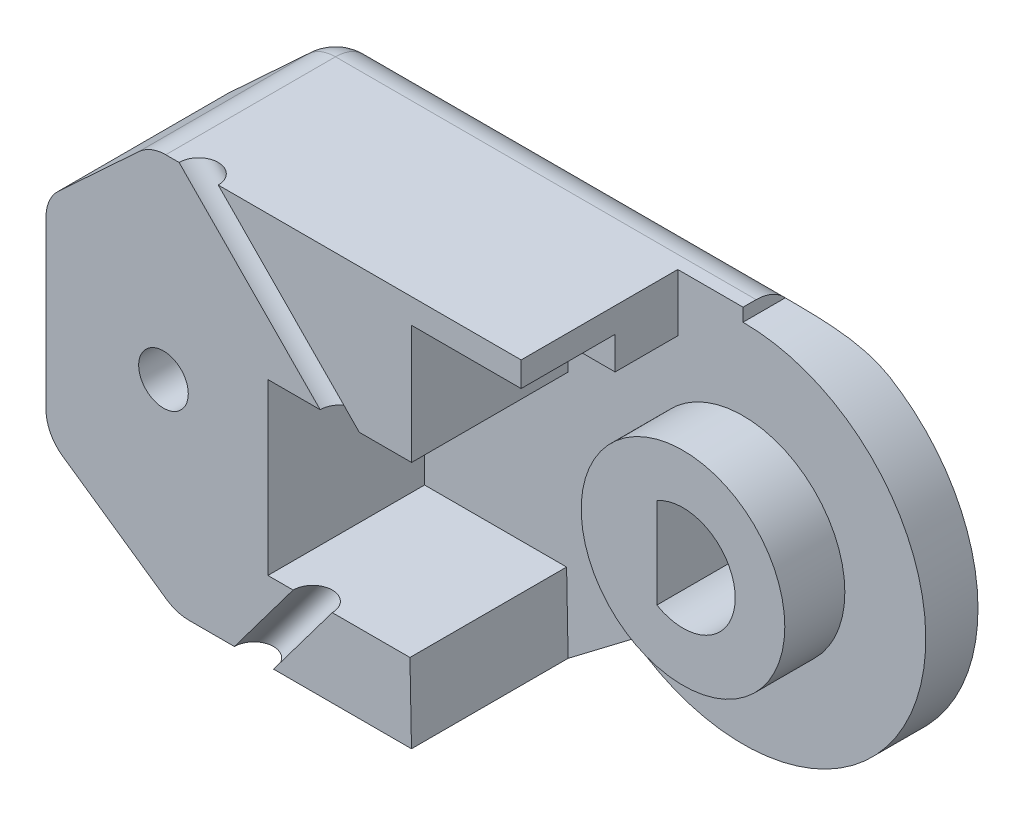
SolidWorks part; units mm, degrees
ref_plane "Front Plane" through (0, 0, 0) normal (0, 0, 1) x (1, 0, 0)
ref_plane "Top Plane" through (0, 0, 0) normal (0, 1, 0) x (1, 0, 0)
ref_plane "Right Plane" through (0, 0, 0) normal (1, 0, 0) x (0, 0, -1)
sketch "Sketch2" plane through (0, 0, 0) normal (0, 0, 1) x (1, 0, 0)
  line L1 (-2.5, 7.5) -> (-16.7, 7.5)
  line L2 (-20.7, 3.7934) -> (-20.7, -4.0316)
  line L3 (-15.7, -7.5) -> (-6.7, -7.5)
  line L4 (-6.7, -7.5) -> (-4.2, -5.6)
  line L5 (-2.5, 7.5) -> (0, 7.5)
  line L7 (0, 7) -> (0, 7.5)
  line L8 (-20.7, 3.7934) -> (-16.7, 7.5)
  line L9 (-20.7, -4.0316) -> (-15.7, -7.5)
  arc A1 (-4.2, -5.6) -> (7, 0) centre (0, 0) ccw
  arc A2 (7, 0) -> (0, 7) centre (0, 0) ccw
  dimension "D1" = 7
  dimension "D2" = 4
  dimension "D3" = 5
  dimension "D4" = 7.5
  dimension "D5" = 15
  dimension "D7" = 2.5
  dimension "D8" = 14
extrude "Boss-Extrude1" add sketch "Sketch2" along normal blind 2 contours A1 A2 L7 L5 L1 L8 L2 L9 L3 L4
sketch "Sketch4" plane through (0, 0, 2) normal (0, 0, 1) x (1, 0, 0)
  line L7 (-15.7, -7.5) -> (-6.7, -7.5)
  line L8 (-6.7, -7.5) -> (-6.7591, -4.5)
  line L9 (-6.7591, -4.5) -> (-12.2, -4.5)
  line L10 (-16.7, 7.5) -> (-2.5, 7.5)
  line L13 (-6.6963, 2) -> (-6.6963, 5.3)
  line L14 (-6.6963, 5.3) -> (-2.5, 5.3)
  line L21 (-20.7, -4.0316) -> (-15.7, -7.5)
  line L24 (-16.7, 7.5) -> (-20.7, 3.7934)
  line L25 (-20.7, -4.0316) -> (-20.7, 3.7934)
  line L26 (-12.2, 2) -> (-6.6963, 2)
  line L29 (-12.2, 2) -> (-12.2, -4.5)
  line L30 (-2.5, 7.5) -> (-2.5, 5.3)
  dimension "D1" = 8.5
  dimension "D2" = 2.5
  dimension "D3" = 3
extrude "Boss-Extrude2" add sketch "Sketch4" along normal blind 6
ref_point "Point1"
sketch "Sketch22" plane through (0, 0, 2) normal (0, 0, 1) x (1, 0, 0)
  line L0 (0, 5.3) -> (-14, 5.3) construction
  line L1 (0, 4) -> (-14, 4) construction
  line L2 (-14, 4) -> (-14, 5.3) construction
  circle A0 centre (0, 0) radius 5.3 construction
  circle A1 centre (0, 0) radius 4 construction
  dimension "D1" = 14
  dimension "D2" = 10.6
  dimension "D3" = 8
sketch "Sketch24" plane through (0, 0, 2) normal (0, 0, 1) x (1, 0, 0)
  circle A0 centre (0, 0) radius 3.9
  dimension "D1" = 7.8
extrude "Boss-Extrude5" add sketch "Sketch24" along normal blind 2.3
sketch "Sketch29" plane through (-6.6963, 0, 0) normal (1, 0, 0) x (0, 0, -1)
  line L0 (-1.9279, 3.9758) -> (-8, 3.9758) construction
  line L1 (-8, 2) -> (-8, 5.3) construction
sketch "Sketch30" plane through (-6.6963, 0, 0) normal (1, 0, 0) x (0, 0, -1)
  line L0 (-4.4659, 3.9758) -> (-4.4659, 5.3)
  line L1 (-4.4659, 3.9758) -> (-2.0573, 3.9758)
  line L2 (-4.4659, 5.3) -> (-2.0573, 5.3)
  line L3 (-2.0573, 3.9758) -> (-2.0573, 5.3)
  line L4 (-1.9279, 3.9758) -> (-8, 3.9758) construction
  line L5 (-8, 5.3) -> (-2, 5.3) construction
extrude "Cut-Extrude12" cut sketch "Sketch30" against normal blind 8
ref_plane "Plane1" through (0, 0, 8) normal (0, 0, 1) x (1, 0, 0)
sketch "Sketch8" plane through (0, 0, 2) normal (0, 0, 1) x (1, 0, 0)
  circle A1 centre (0, 0) radius 3.8
  circle A2 centre (0, 0) radius 2.5
sketch "Sketch28" plane through (0, 0, 4.3) normal (0, 0, 1) x (1, 0, 0)
  line L0 (-1, 1.7321) -> (-1, -1.7321)
  arc A0 (-1, -1.7321) -> (-1, 1.7321) centre (0, 0) ccw
  dimension "D1" = 1
  dimension "D2" = 2
extrude "Cut-Extrude11" cut sketch "Sketch28" against normal through all
sketch "Sketch33" plane through (0, 0, 8) normal (0, 0, 1) x (1, 0, 0)
  line L0 (-9.4481, 2) -> (-2.4157, -5.1566) construction
  line L1 (-12.2, 2) -> (-6.6963, 2) construction
  line L2 (-10.4836, -4.5) -> (-4.8246, 3.0469) construction
  line L3 (-6.7591, -4.5) -> (-12.2, -4.5) construction
fillet "Fillet1" radius 1.5 9 edges at (-11.2, -7.5, 0) (-8.35, 7.5, 0) (-18.7, 5.6467, 0) (-18.2, -5.7658, 0) (-20.7, -0.1191, 0) (-15.7, -7.5, 4) (-20.7, -4.0316, 4) (-20.7, 3.7934, 4) (-16.7, 7.5, 4)
sketch "Sketch34" plane through (0, 2, 0) normal (0, -1, 0) x (1, 0, 0)
  circle A0 centre (-9.4481, 8) radius 0.75
  dimension "D1" = 1.5
extrude "Cut-Extrude13" cut sketch "Sketch34" along direction (0.7009, -0.7133, 0) on the side against the normal blind 8
sketch "Sketch35" plane through (0, -4.5, 0) normal (0, 1, 0) x (1, 0, 0)
  circle A0 centre (-10.4836, -8) radius 0.75
extrude "Cut-Extrude14" cut sketch "Sketch35" along direction (0.5999, 0.8001, 0) on the side against the normal blind 8
sketch "Sketch36" plane through (0, 0, 8) normal (0, 0, 1) x (1, 0, 0)
  line L2 (-12.2, -4.5) -> (-12.2, 2) construction
  circle A0 centre (-16.2, 0) radius 0.95
  dimension "D1" = 4
extrude "Cut-Extrude15" cut sketch "Sketch36" against normal blind 8
sketch "Sketch37" plane through (0, 0, 0) normal (0, 0, -1) x (-1, 0, 0)
  circle A0 centre (16.2, 0) radius 2
extrude "Cut-Extrude16" cut sketch "Sketch37" against normal blind 5
sketch "Sketch38" plane through (0, 0, 8) normal (0, 0, 1) x (1, 0, 0)
  line L0 (-6.6963, 5.3) -> (-2.5, 5.3)
  line L1 (-6.6963, 5.3) -> (-6.6963, 6.55)
  line L2 (-2.5, 5.3) -> (-2.5, 6.55)
  line L3 (-6.6963, 6.55) -> (-2.5, 6.55)
  dimension "D1" = 1.25
extrude "Cut-Extrude17" cut sketch "Sketch38" against normal blind 3.6
